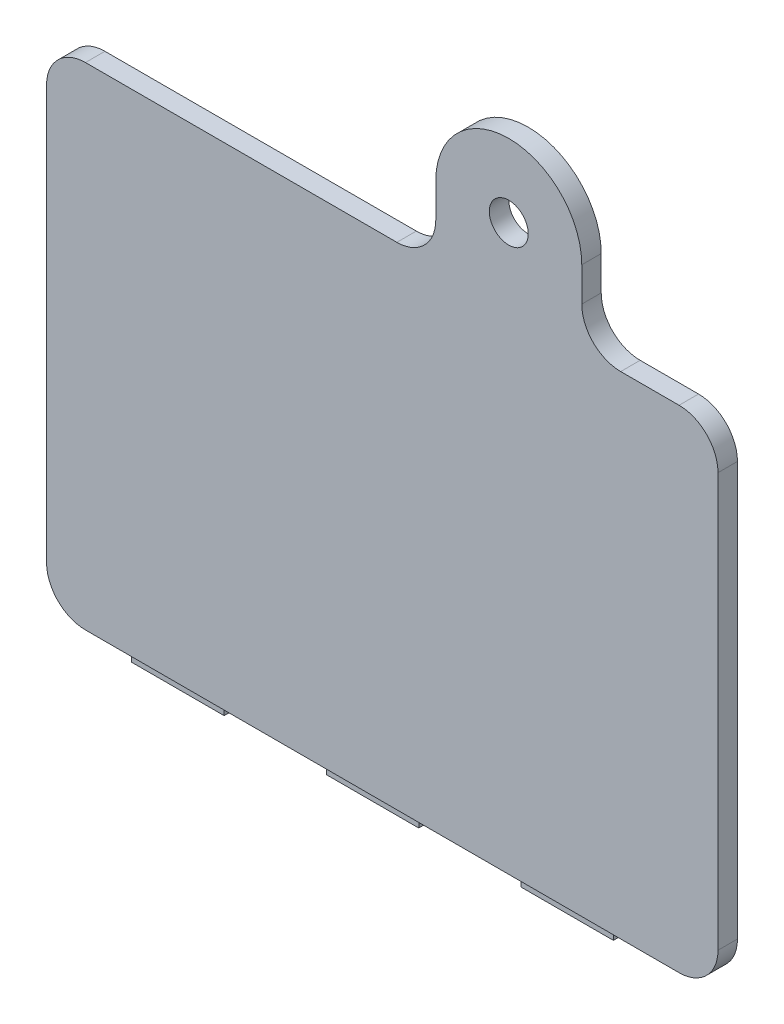
SolidWorks part; units mm, degrees
ref_plane "Plan de face" through (0, 0, 0) normal (0, 0, 1) x (1, 0, 0)
ref_plane "Plan de dessus" through (0, 0, 0) normal (0, 1, 0) x (1, 0, 0)
ref_plane "Plan de droite" through (0, 0, 0) normal (1, 0, 0) x (0, 0, -1)
sketch "Esquisse1" plane through (0, 0, 0) normal (0, 0, 1) x (1, 0, 0)
  line L0 (8.5, 25.25) -> (8.5, 32.75)
  line L1 (-37.5, 25.25) -> (8.5, 25.25)
  line L2 (-37.5, 25.25) -> (-37.5, -25.25)
  line L3 (-37.5, -25.25) -> (37.5, -25.25)
  line L4 (37.5, 25.25) -> (37.5, -25.25)
  line L5 (-37.5, 25.25) -> (37.5, -25.25) construction
  line L6 (-37.5, -25.25) -> (37.5, 25.25) construction
  line L7 (23.5, 32.75) -> (23.5, 25.25)
  line L8 (23.5, 25.25) -> (37.5, 25.25)
  line L9 (8.5, 25.25) -> (23.5, 25.25) construction
  arc A0 (8.5, 32.75) -> (23.5, 32.75) centre (16, 32.75) cw
  circle A1 centre (16, 32.75) radius 2
  point P0 (0, 0)
  point P11 (16, 25.25)
  dimension "D6" = 4
  dimension "D1" = 75
  dimension "D2" = 50.5
  dimension "D3" = 16
  dimension "D4" = 15
  dimension "D5" = 7.5
extrude "Boss.-Extru.1" add sketch "Esquisse1" along normal blind 2 contours A0 L0 L1 L2 L3 L4 L8 L7 A1 region at (0.7577, 1.5156, 0)
sketch "Esquisse2" plane through (0, -25.25, 0) normal (0, -1, 0) x (1, 0, 0)
  line L0 (-37.5, 0) -> (37.5, 0) construction
  line L1 (4.75, 0) -> (-4.75, 0)
  line L2 (4.75, 0) -> (4.75, -2)
  line L3 (4.75, -2) -> (-4.75, -2)
  line L4 (-4.75, 0) -> (-4.75, -2)
  line L5 (37.5, 0) -> (24.75, -2) construction
  line L6 (-15.25, 0) -> (-24.75, 0)
  line L7 (-15.25, 0) -> (-15.25, -2)
  line L8 (-15.25, -2) -> (-24.75, -2)
  line L9 (-24.75, 0) -> (-24.75, -2)
  line L10 (15.25, 0) -> (24.75, 0)
  line L11 (15.25, 0) -> (15.25, -2)
  line L12 (15.25, -2) -> (24.75, -2)
  line L13 (24.75, 0) -> (24.75, -2)
  line L16 (-24.75, -2) -> (-37.5, 0) construction
  point P15 (20, -2)
  point P19 (0, -2)
  point P20 (-20, -2)
  dimension "D1" = 2
  dimension "D2" = 20
  dimension "D3" = 20
  dimension "D4" = 9.5
extrude "Boss.-Extru.2" add sketch "Esquisse2" along normal mid plane 5
chamfer "Chanfrein1" distance 2 angle 45 3 edges at (-20, -22.75, 0) (0, -22.75, 0) (20, -22.75, 0)
sketch "Esquisse4" plane through (0, 0, 2) normal (0, 0, 1) x (1, 0, 0)
  line L0 (-37.5, -25.25) -> (37.5, -25.25) construction
  line L1 (-37.5, 25.25) -> (-31.5, 25.25)
  line L2 (-37.5, 25.25) -> (-37.5, -25.25)
  line L3 (-37.5, -25.25) -> (-31.5, -25.25)
  line L4 (-31.5, 25.25) -> (-31.5, -25.25)
  dimension "D1" = 6
extrude "Enlèv. mat.-Extru.2" cut sketch "Esquisse4" against normal up to next
fillet "Congé1" radius 4 6 edges at (37.5, -25.25, 1) (23.5, 25.25, 1) (8.5, 25.25, 1) (37.5, 25.25, 1) (-31.5, -25.25, 1) (-31.5, 25.25, 1)
